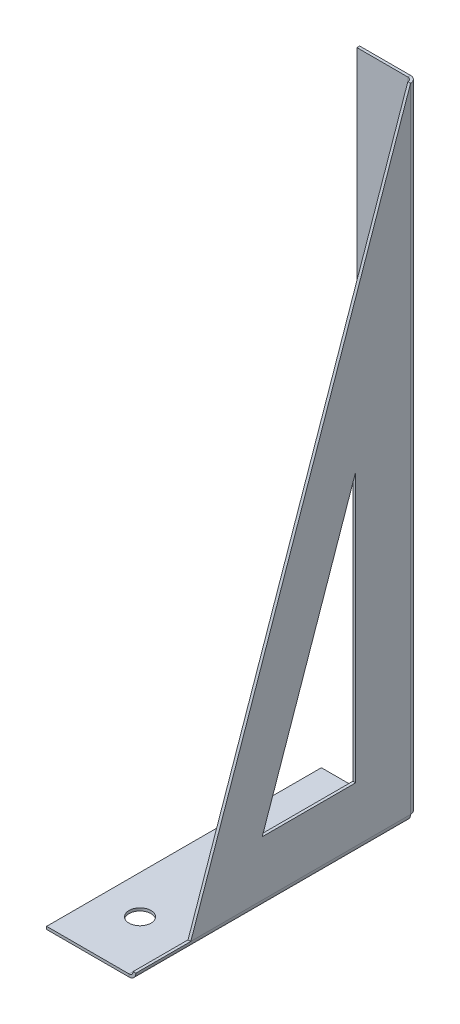
SolidWorks part; units mm, degrees
note: The reader was unsure of these and kept them because the rebuilt part matched: flange length of "Edge-Flange1", "Edge-Flange2".
ref_plane "Front Plane" through (0, 0, 0) normal (0, 0, 1) x (1, 0, 0)
ref_plane "Top Plane" through (0, 0, 0) normal (0, 1, 0) x (1, 0, 0)
ref_plane "Right Plane" through (0, 0, 0) normal (1, 0, 0) x (0, 0, -1)
sketch "Sketch2" plane through (0, 0, 0) normal (0, 1, 0) x (1, 0, 0)
  line L1 (-15, 0) -> (0, 0)
  line L2 (-15, 0) -> (-15, -50)
  line L3 (-15, -50) -> (0, -50)
  line L4 (0, 0) -> (0, -50)
  dimension "D1" = 50
  dimension "D2" = 15
sheet metal parameters "Sheet-Metal1" thickness 0.5 parameters "D1"=0.7366
base flange "Base-Flange1" sketch "Sketch2" thickness 0.5 reverse thickness direction no parameters "D1"=0.7366
edge flange "Edge-Flange1" sketch "Sketch18" flange angle 90 flange length 116 flange position bend outside bend radius 0.7366 thickness 0.5 parameters "D6"=10
bend "EdgeBend3" bend radius 0.7366 bend angle 90 parameters "D5"=3
sketch "Sketch18" plane through (0, 0, 0) normal (1, 0, 0) x (0, 0, -1)
  line L0 (-50, 0) -> (0, 0) construction
  line L1 (-50, 0) -> (0, 0)
  line L2 (-50, 0) -> (-50, 116)
  line L3 (-50, 116) -> (0, 116)
  line L4 (0, 116) -> (0, 0)
sketch "Sketch19" plane through (0.7366, 0, 0) normal (-1, 0, 0) x (0, 0, 1)
  line L0 (50, 0.7366) -> (40, 0.7366)
  line L1 (50, 0.7366) -> (0, 0.7366) construction
  line L2 (40, 0.7366) -> (0, 116)
  line L3 (0, 116) -> (50, 116)
  line L4 (0, 116) -> (50, 116) construction
  line L5 (50, 116) -> (50, 0.7366) construction
  line L6 (50, 116) -> (50, 0.7366)
  dimension "D1" = 10
extrude "Cut-Extrude1" cut sketch "Sketch19" against normal blind 10
sketch "Sketch21" plane through (0.7366, 0, 0) normal (-1, 0, 0) x (0, 0, 1)
  line L0 (10, 10.7366) -> (10, 59.7366)
  line L1 (0, 0.7366) -> (0, 116) construction
  line L3 (10, 10.7366) -> (27, 10.7366)
  line L4 (40, 0.7366) -> (0, 0.7366) construction
  line L5 (27, 10.7366) -> (10, 59.7366)
  dimension "D1" = 49
  dimension "D2" = 10
  dimension "D3" = 10
  dimension "D4" = 17
extrude "Cut-Extrude2" cut sketch "Sketch21" against normal blind 10
sketch "Sketch22" plane through (0, 0, 0) normal (0, 1, 0) x (1, 0, 0)
  line L0 (-15, -50) -> (0, -50) construction
  line L1 (-15, 0) -> (-15, -50) construction
  line L2 (0, 0) -> (-15, 0) construction
  circle A0 centre (-8, -40) radius 2
  circle A1 centre (-8, -7) radius 2
  point P2 (-7.5, -50)
  dimension "D1" = 10
  dimension "D3" = 4
  dimension "D4" = 7
  dimension "D6" = 4
  dimension "D2" = 7
  dimension "D5" = 7
extrude "Cut-Extrude3" cut sketch "Sketch22" against normal blind 10
edge flange "Edge-Flange2" sketch "Sketch25" flange angle 90 flange length 10 flange position bend outside bend radius 0.7366 thickness 0.5 parameters "D6"=10
sketch "Sketch25" plane through (0.7366, 0, 0) normal (0, 0, -1) x (0, -1, 0)
  line L0 (-0.7366, 0) -> (-116, 0) construction
  line L1 (-0.7366, 0) -> (-116, 0)
  line L2 (-116, 0) -> (-116, 10)
  line L3 (-116, 10) -> (-0.7366, 10)
  line L4 (-0.7366, 10) -> (-0.7366, 0)
bend "EdgeBend4" bend radius 0.7366 bend angle 90 parameters "D5"=4
flat pattern "Flat-Pattern1" [suppressed]
sketch "Bend-Lines1" plane through (0, 0, 0) normal (0, 1, 0) x (1, 0, 0)
  point P0 (-16.5497, 0.7749)
  point P1 (-131.8131, 0.7749)
  point P2 (-15.7749, -50)
  point P3 (-15.7749, 0)
sketch3d "Bounding-Box1" [suppressed]
  line L0 (0, -50, 0) -> (-131.8131, -50, 0) construction
  line L1 (0, 12.8131, 0) -> (-131.8131, 12.8131, 0) construction
  line L2 (0, -50, 0) -> (0, 12.8131, 0) construction
  line L3 (-131.8131, -50, 0) -> (-131.8131, 12.8131, 0) construction
bend of the flat pattern "Flatten-<EdgeBend3>1"
bend of the flat pattern "Flatten-<EdgeBend4>1"
